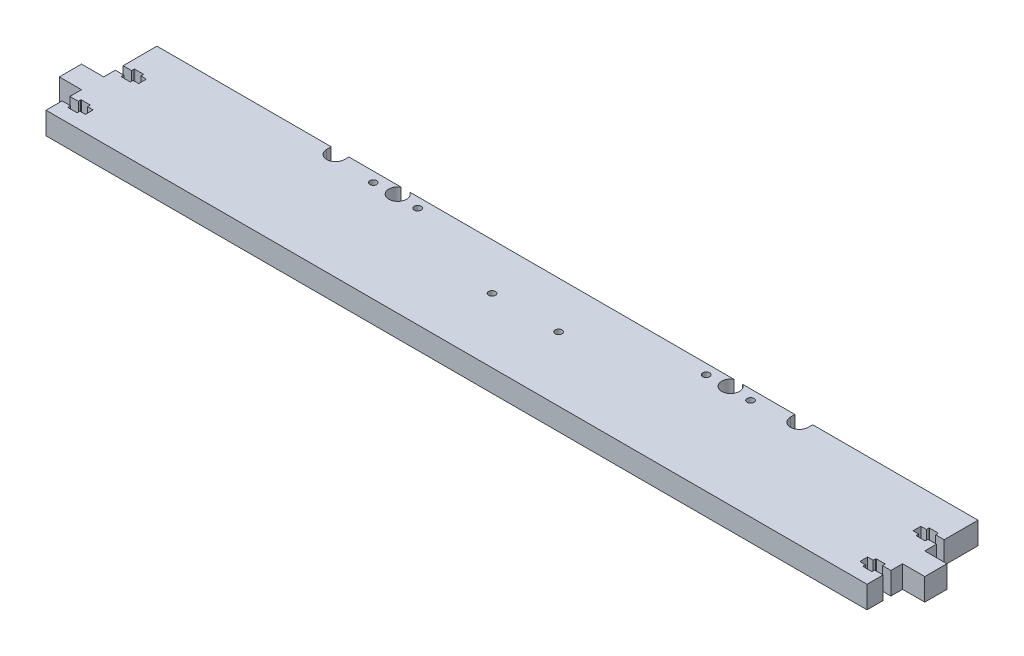
SolidWorks part; units mm, degrees
ref_plane "Front Plane" through (0, 0, 0) normal (0, 0, 1) x (1, 0, 0)
ref_plane "Top Plane" through (0, 0, 0) normal (0, 1, 0) x (1, 0, 0)
ref_plane "Right Plane" through (0, 0, 0) normal (1, 0, 0) x (0, 0, -1)
sketch "Sketch1" plane through (0, 0, 0) normal (0, 1, 0) x (1, 0, 0)
  line L0 (0, 25) -> (0, -25)
  line L1 (-185, 25) -> (0, 25)
  line L2 (-185, 25) -> (-185, -25) construction
  line L3 (-185, -25) -> (0, -25)
  line L4 (-185, -4) -> (-195, -4) construction
  line L5 (-185, 25) -> (0, 0) construction
  line L6 (-185, -25) -> (0, 0) construction
  line L7 (-185, -9) -> (-195, -9)
  line L8 (-195, -9) -> (-195, 1)
  line L9 (-195, 1) -> (-185, 1)
  line L10 (-185, 1) -> (-185, 25)
  line L11 (-185, -9) -> (-185, -25)
  line L47 (0, -25) -> (0, 25) construction
  line L89 (0, -25) -> (0, 25) construction
  point P0 (0, 0)
  dimension "D1" = 185
  dimension "D25" = 25
  dimension "D4" = 50
  dimension "D3" = 21
  dimension "D5" = 10
  dimension "D6" = 10
  dimension "D7" = 5
extrude "MainBody" add sketch "Sketch1" along normal blind 10 contours L3 region at (-93.5428, 0, 0.0428)
sketch "Sketch5" plane through (0, 10, 0) normal (0, 1, 0) x (1, 0, 0)
  line L0 (-185, 8) -> (-174.5, 8) construction
  line L1 (-185, 1) -> (-185, 25) construction
  line L2 (-185, 9.75) -> (-174.5, 9.75) construction
  line L3 (-174.5, 9.75) -> (-174.5, 6.25) construction
  line L4 (-174.5, 6.25) -> (-185, 6.25) construction
  line L5 (-185, 9.75) -> (-181.2, 9.75)
  line L6 (-181.2, 9.75) -> (-181.2, 10.75)
  line L7 (-180.95, 11) -> (-177.25, 11)
  line L8 (-177, 10.75) -> (-177, 9.75)
  line L9 (-177, 9.75) -> (-174.5, 9.75)
  line L10 (-174.5, 9.75) -> (-174.5, 6.25)
  line L11 (-185, 6.25) -> (-185, 9.75)
  line L12 (-195, -9) -> (-195, 1) construction
  line L13 (-185, 6.25) -> (-174.5, 6.25) construction
  line L14 (-177, 6.25) -> (-174.5, 6.25)
  line L15 (-177, 5.25) -> (-177, 6.25)
  line L16 (-180.95, 5) -> (-177.25, 5)
  line L17 (-181.2, 6.25) -> (-181.2, 5.25)
  line L18 (-185, 6.25) -> (-181.2, 6.25)
  line L19 (-185, 1) -> (-185, -9) construction
  line L20 (-195, -4) -> (-185, -4) construction
  line L21 (-195, -9) -> (-195, 1) construction
  line L22 (-185, -14.25) -> (-174.5, -14.25) construction
  line L23 (-174.5, -14.25) -> (-185, -14.25) construction
  line L24 (-174.5, -17.75) -> (-174.5, -14.25) construction
  line L25 (-185, -17.75) -> (-174.5, -17.75) construction
  line L26 (-185, -16) -> (-174.5, -16) construction
  line L27 (-185, -14.25) -> (-181.2, -14.25)
  line L28 (-181.2, -14.25) -> (-181.2, -13.25)
  line L29 (-180.95, -13) -> (-177.25, -13)
  line L30 (-177, -13.25) -> (-177, -14.25)
  line L31 (-177, -14.25) -> (-174.5, -14.25)
  line L32 (-185, -14.25) -> (-185, -17.75)
  line L33 (-174.5, -17.75) -> (-174.5, -14.25)
  line L34 (-177, -17.75) -> (-174.5, -17.75)
  line L35 (-177, -18.75) -> (-177, -17.75)
  line L36 (-180.95, -19) -> (-177.25, -19)
  line L37 (-181.2, -17.75) -> (-181.2, -18.75)
  line L38 (-185, -17.75) -> (-181.2, -17.75)
  line L39 (-185, 6.25) -> (-174.5, 6.25) construction
  arc A0 (-177.25, 11) -> (-177, 10.75) centre (-177.25, 10.75) cw
  arc A1 (-181.2, 10.75) -> (-180.95, 11) centre (-180.95, 10.75) cw
  arc A2 (-181.2, 5.25) -> (-180.95, 5) centre (-180.95, 5.25) ccw
  arc A3 (-177.25, 5) -> (-177, 5.25) centre (-177.25, 5.25) ccw
  arc A4 (-177.25, -13) -> (-177, -13.25) centre (-177.25, -13.25) cw
  arc A5 (-181.2, -13.25) -> (-180.95, -13) centre (-180.95, -13.25) cw
  arc A6 (-181.2, -18.75) -> (-180.95, -19) centre (-180.95, -18.75) ccw
  arc A7 (-177.25, -19) -> (-177, -18.75) centre (-177.25, -18.75) ccw
  point P6 (-195, -4)
  point P17 (-177, 11)
  point P20 (-181.2, 11)
  point P29 (-181.2, 5)
  point P30 (-177, 5)
  point P61 (-177, -13)
  point P62 (-181.2, -13)
  point P63 (-181.2, -19)
  point P64 (-177, -19)
  dimension "D8" = 0.25
  dimension "D1" = 10.5
  dimension "D2" = 1.75
  dimension "D4" = 4.2
  dimension "D5" = 8
  dimension "D6" = 3
  dimension "D7" = 12
extrude "ScrewCutouts" cut sketch "Sketch5" against normal through all
mirror "Mirror1" about plane through (0, 0, 0) normal (1, 0, 0) of "ScrewCutouts", "MainBody"
sketch "Sketch3" plane through (0, 10, 0) normal (0, 1, 0) x (1, 0, 0)
  line L0 (2, 25) -> (2, -25) construction
  line L1 (-185, 25) -> (185, 25) construction
  line L2 (-185, -25) -> (185, -25) construction
  line L3 (-63, 20.5) -> (-83, 20.5) construction
  line L4 (-73, 17.5) -> (-73, 25.5) construction
  line L5 (77, 17.5) -> (77, 25.5) construction
  line L6 (67, 20.5) -> (87, 20.5) construction
  circle A0 centre (-73, 21.5) radius 4
  circle A1 centre (-83, 20.5) radius 1.55
  circle A2 centre (-63, 20.5) radius 1.55
  circle A3 centre (67, 20.5) radius 1.55
  circle A4 centre (87, 20.5) radius 1.55
  circle A5 centre (77, 21.5) radius 4
  dimension "D2" = 8
  dimension "D4" = 3.1
  dimension "D1" = 3.5
  dimension "D5" = 75
  dimension "D6" = 2
  dimension "D3" = 10
  dimension "D7" = 1
extrude "RodCutouts" cut sketch "Sketch3" against normal through all
sketch "Sketch6" plane through (0, 10, 0) normal (0, 1, 0) x (1, 0, 0)
  line L0 (-73, 21.5) -> (77, 21.5) construction
  line L1 (2, 21.5) -> (2, -25) construction
  line L2 (-185, -25) -> (185, -25) construction
  line L3 (17, 4) -> (-13, 4) construction
  line L4 (-71.0635, 25) -> (75.0635, 25) construction
  circle A0 centre (-13, 4) radius 1.55
  circle A1 centre (17, 4) radius 1.55
  point P13 (2, 4)
  dimension "D3" = 21
  dimension "D1" = 3.1
  dimension "D2" = 15
extrude "Cut-Extrude1" cut sketch "Sketch6" against normal through all
sketch "Sketch7" plane through (0, 10, 0) normal (0, 1, 0) x (1, 0, 0)
  line L0 (-73, 21.5) -> (77, 21.5) construction
  line L1 (2, 21.5) -> (2, -25) construction
  line L3 (-102.5, 25) -> (-102.5, 23) construction
  line L4 (-185, 25) -> (-74.9365, 25) construction
  line L5 (-98.5, 25) -> (-98.5, 23)
  line L6 (-106.5, 25) -> (-106.5, 23)
  line L7 (106.5, 25) -> (106.5, 23) construction
  line L8 (102.5, 25) -> (102.5, 23)
  line L9 (110.5, 25) -> (110.5, 23)
  line L12 (-185, -25) -> (185, -25) construction
  arc A0 (-98.5, 25) -> (-106.5, 25) centre (-102.5, 25) ccw
  arc A1 (-106.5, 23) -> (-98.5, 23) centre (-102.5, 23) ccw
  arc A2 (102.5, 25) -> (110.5, 25) centre (106.5, 25) cw
  arc A3 (110.5, 23) -> (102.5, 23) centre (106.5, 23) cw
  point P12 (-102.5, 24)
  point P19 (106.5, 24)
  dimension "D1" = 4
  dimension "D2" = 2
  dimension "D3" = 104.5
extrude "BedAdjustmentScrewCutout" cut sketch "Sketch7" against normal through all
equation "\"Y-ROD-SPACING\"=75"
equation "\"Y-BED-OFFSET\"=2"
equation "\"T-SLOT-NUT-FILLET-RADIUS\"=0.25"
equation "\"T-SLOT-SCREW-SHAFT-RADIUS\"=1.75"
equation "\"T-SLOT-SCREW-SHAFT-CUTOUT-LENGTH\"=10.5"
equation "\"T-SLOT-NUT-DEPTH\"=4.2"
equation "\"T-SLOT-NUT-WIDTH\"=3"
equation "\"T-SLOT-NUT-END-DISTANCE\"=8"
equation "\"ACRYLIC-TAB-CUTOUT-SIZE\"=\"ACRYLIC-THICKNESS\"+\"ACRYLIC-TAB-TOLERANCE\"*2"
equation "\"ACRYLIC-M3-HOLE\"=3.1"
equation "\"D1@Sketch5\"=\"T-SLOT-SCREW-SHAFT-CUTOUT-LENGTH\""
equation "\"D2@Sketch5\"=\"T-SLOT-SCREW-SHAFT-RADIUS\""
equation "\"D4@Sketch5\"=\"T-SLOT-NUT-DEPTH\""
equation "\"D5@Sketch5\"=\"T-SLOT-NUT-END-DISTANCE\""
equation "\"D6@Sketch5\"=\"T-SLOT-NUT-WIDTH\""
equation "\"D8@Sketch5\"=\"T-SLOT-NUT-FILLET-RADIUS\""
equation "\"D4@Sketch3\"=\"ACRYLIC-M3-HOLE\""
equation "\"D5@Sketch3\"=\"Y-ROD-SPACING\""
equation "\"D6@Sketch3\"=\"Y-BED-OFFSET\""
equation "\"Y-BED-ROD-INSET\"=3.5"
equation "\"D1@Sketch3\"=\"Y-BED-ROD-INSET\""
equation "\"SMOOTHROD-CAP-SCREW-DISTANCE\"=20"
equation "\"D3@Sketch3\"=\"SMOOTHROD-CAP-SCREW-DISTANCE\"/2"
equation "\"ACRYLIC-TAB-WIDTH\"=\"ACRYLIC-THICKNESS\""
equation "\"FRAME-WIDTH-INNER\"=370"
equation "\"D6@Sketch1\"=\"ACRYLIC-TAB-WIDTH\""
equation "\"D5@Sketch1\"=\"ACRYLIC-TAB-WIDTH\""
equation "\"D1@Sketch1\"=\"FRAME-WIDTH-INNER\"/2"
equation "\"X-ROD-SPACING\"=45"
equation "\"Z-ROD-SPACING\"=17.5"
equation "\"ACRYLIC-THICKNESS\"=10"
equation "\"ACRYLIC-THICKNESS2\"=4.5"
equation "\"NEMA17-HOLE-SPACING\"=31"
equation "\"NEMA17-CENTRAL-CUTOUT\"=22.5"
equation "\"Z-BRACKET-REACH\"=55"
equation "\"TOP-BRACKET-SPACING\"=40"
equation "\"SMOOTHROD-X-LENGTH\"=350"
equation "\"SMOOTHROD-Y-LENGTH\"=350"
equation "\"SMOOTHROD-Z-LENGTH\"=350"
equation "\"SMOOTHROD-TIGHTENING-HEADROOM\"=.25"
equation "\"LEADSCREW-Z-LENGTH\"=300"
equation "\"SCREW-LENGTH-FRAME\"=\"ACRYLIC-THICKNESS\" + 10"
equation "\"SCREW-HEAD-RADIUS\"=6"
equation "\"PRINTED-X-SMOOTHROD-DIAMETER\"=8.2"
equation "\"PRINTED-X-SMOOTHROD-CUTOUT\"=10"
equation "\"PRINTED-X-BASE-HEIGHT\"=10"
equation "\"PRINTED-LM8UU-CUTOUT-SIZE\"=15.25"
equation "\"PRINTED-LM8UU-CUTOUT-LENGTH\"=24.5"
equation "\"PRINTED-X-IDLER-HEIGHT\"=16"
equation "\"PSU-MOUNTING-WIDTH\"=95"
equation "\"PSU-MOUNTING-HEIGHT\"=177"
equation "\"D1@MainBody\"=\"ACRYLIC-THICKNESS\""
equation "\"D7@Sketch1\"=\"ACRYLIC-TAB-WIDTH\"/2"
equation "\"D1@Sketch6\"=\"ACRYLIC-M3-HOLE\""
equation "\"Y-BELT-TO-ROD-DISTANCE\"=20"
equation "\"Y-BED-SCREW-SPACING\"=209"
equation "\"Z-ROD-INSET\"=16"
equation "\"SPOOL-HOLDER-ROD-SPACING\"=150"
equation "\"D3@Sketch7\"=\"Y-BED-SCREW-SPACING\"/2"
equation "\"Y-BED-SCREW-CUTOUT-SLOT-HEIGHT\"=2"
equation "\"D2@Sketch7\"=\"Y-BED-SCREW-CUTOUT-SLOT-HEIGHT\""
equation "\"ACRYLIC-TAB-TOLERANCE\"=.1"
equation "\"SCREW-LENGTH-MOTOR\"=\"ACRYLIC-THICKNESS\" + 5"
equation "\"SCREW-LENGTH-EXTRUDER\"=28"
equation "\"PRINTED-M3-HOLE\"=3.5"
equation "\"ACRYLIC-X-CARRIAGE-WIDTH\"=55"
equation "\"ACRYLIC-X-CARRIAGE-HEIGHT\"=75"
equation "\"ACRYLIC-X-CARRIAGE-LM8UU-CUTOUT-WIDTH\"=24.25"
equation "\"ACRYLIC-X-CARRIAGE-LM8UU-CUTOUT-HEIGHT\"=11.5"
equation "\"ACRYLIC-X-CARRIAGE-SCREW-SPACING-X\"=15"
equation "\"ACRYLIC-X-CARRIAGE-SCREW-SPACING-Y\"=33"
equation "\"ACRYLIC-X-CARRIAGE-CENTER-TAB-SPACING\"=14"
equation "\"ACRYLIC-X-CARRIAGE-EXTRUDER-OFFSET\"=26"
equation "\"ACRYLIC-X-CARRIAGE-EXTRUDER-ANGLE\"=90"
equation "\"ACRYLIC-X-CARRIAGE-EXTRUDER-SHELF-DEPTH\"=\"ACRYLIC-X-CARRIAGE-EXTRUDER-OFFSET\" + 28"
equation "\"ACRYLIC-X-CARRIAGE-EXTRUDER-BRACE-SPACING\"=23"
equation "\"ACRYLIC-X-CARRIAGE-EXTRUDER-BRACE-TAB-OFFSET\"=20"
equation "\"ACRYLIC-X-CARRIAGE-EXTRUDER-BRACE-HEIGHT\"=35"
equation "\"ACRYLIC-X-CARRIAGE-EXTRUDER-BRACE-SCREW-SPACING\"=22"
equation "\"ACRYLIC-X-CARRIAGE-DUAL-WIDTH-MULTIPLIER\"=1.65"
equation "\"ACRYLIC-X-CARRIAGE-DUAL-HOTEND-SPACING\"=42"
equation "\"ACRYLIC-X-CARRIAGE-DUAL-WIDTH\"=103"
equation "\"ACRYLIC-X-CARRIAGE-DUAL-HOTEND-SEPARATION\"=35"
equation "\"ACRYLIC-X-CARRIAGE-DUAL-MOUNT-PLATE-DEPTH\"=76"
equation "\"ACRYLIC-X-CARRIAGE-DUAL-MOUNT-BRACE-WIDTH\"=45"
equation "\"ACRYLIC-X-CARRIAGE-DUAL-MOUNT-SCREW-WIDTH\"=40"
equation "\"BLOWER-FAN-WIDTH\"=15"
